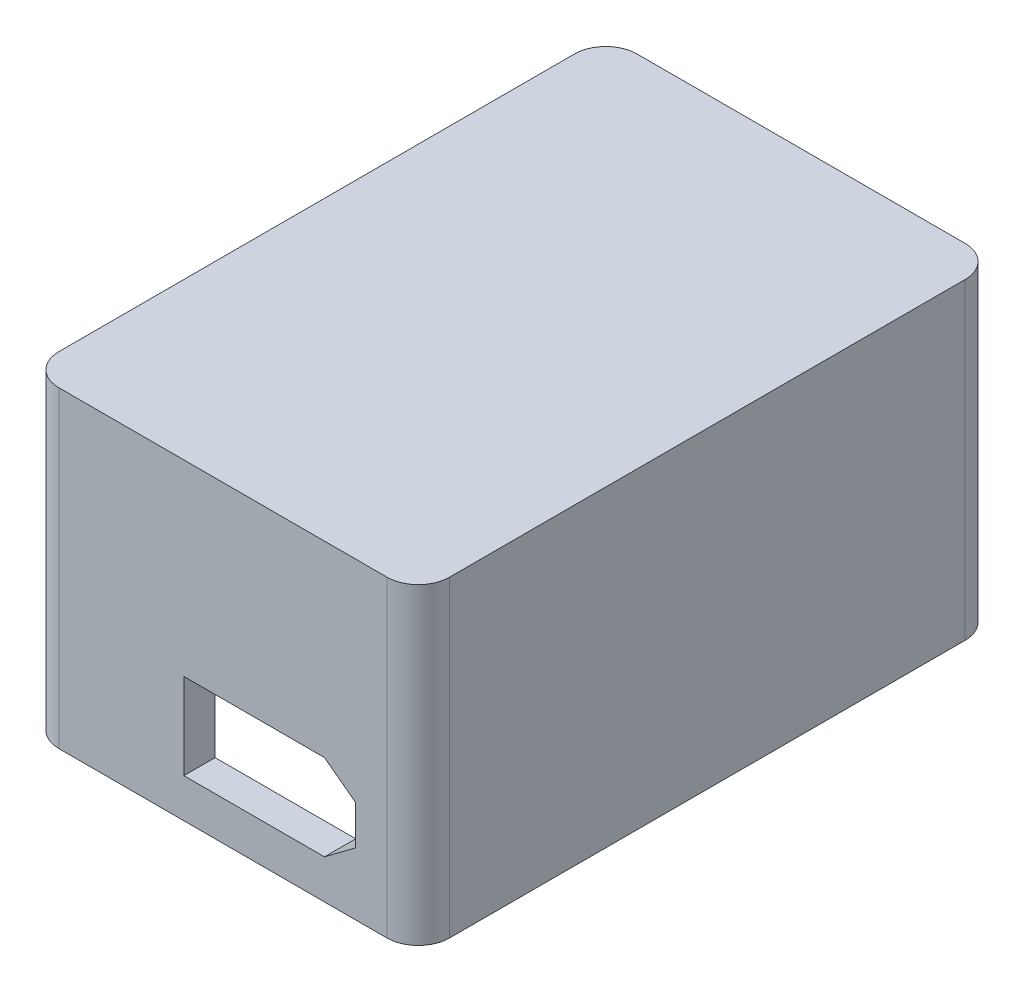
SolidWorks part; units mm, degrees
ref_plane "前视基准面" through (0, 0, 0) normal (0, 0, 1) x (1, 0, 0)
ref_plane "上视基准面" through (0, 0, 0) normal (0, 1, 0) x (1, 0, 0)
ref_plane "右视基准面" through (0, 0, 0) normal (1, 0, 0) x (0, 0, -1)
other "Configuration Table"
sketch "草图1" plane through (0, 0, 0) normal (0, 1, 0) x (1, 0, 0)
  line L1 (-12.5, 18.5) -> (12.5, 18.5)
  line L2 (-12.5, 18.5) -> (-12.5, -18.5)
  line L3 (-12.5, -18.5) -> (12.5, -18.5)
  line L4 (12.5, 18.5) -> (12.5, -18.5)
  line L5 (-12.5, 18.5) -> (12.5, -18.5) construction
  line L6 (-12.5, -18.5) -> (12.5, 18.5) construction
  point P0 (0, 0)
  dimension "D1" = 37
  dimension "D2" = 25
extrude "凸台-拉伸1" add sketch "草图1" along normal blind 20
shell "抽壳1" thickness 2 removed face at (0, 0, 0)
fillet "圆角1" radius 2 4 edges at (-12.5, 10, 18.5) (12.5, 10, 18.5) (-12.5, 10, -18.5) (12.5, 10, -18.5)
sketch "草图3" plane through (0, 0, 16.5) normal (0, 0, -1) x (-1, 0, 0)
  line L0 (10.5, 18) -> (-10.5, 18) construction
  line L1 (-8.5, 8) -> (2.5, 8)
  line L2 (-8.5, 8) -> (-8.5, 2.5)
  line L3 (-8.5, 2.5) -> (2.5, 2.5)
  line L4 (2.5, 8) -> (2.5, 2.5)
  line L5 (-6.5, 8) -> (-8.5, 6.5)
  line L6 (-10.5, 20) -> (-10.5, 0) construction
  line L7 (-8.5, 4) -> (-6.5, 2.5)
  line L8 (0, 0) -> (0, 20) construction
  line L9 (-10.5, 20) -> (10.5, 20) construction
  line L10 (-3.5, 11.4) -> (3.5, 11.4) construction
  line L11 (-3.5, 13) -> (3.5, 13)
  line L12 (-3.5, 9.8) -> (3.5, 9.8)
  arc A0 (-3.5, 13) -> (-3.5, 9.8) centre (-3.5, 11.4) ccw
  arc A1 (3.5, 9.8) -> (3.5, 13) centre (3.5, 11.4) ccw
  point P19 (0, 11.4)
  point P24 (0, 0)
  point P25 (0, 0)
  point P27 (4.9, 14.7597)
  dimension "D10" = 7
  dimension "D12" = 1.8
  dimension "D1" = 11
  dimension "D2" = 5.5
  dimension "D3" = 10
  dimension "D4" = 2
  dimension "D5" = 1.5
  dimension "D6" = 2
  dimension "D7" = 1.5
  dimension "D8" = 2
  dimension "D9" = 3.2
  dimension "D11" = 0
extrude "切除-拉伸1" cut sketch "草图3" against normal through all contours L2 L7 L3 L4 L1 L5 region at (2.7478, 5.25, 16.5)
extrude "切除-拉伸2" cut sketch "草图3<3>" along normal through all contours L12 A1 L11 A0 region at (0, 11.4, 16.5)
sketch "草图3<3>" plane through (0, 0, 16.5) normal (0, 0, -1) x (-1, 0, 0) same geometry as "草图3"
